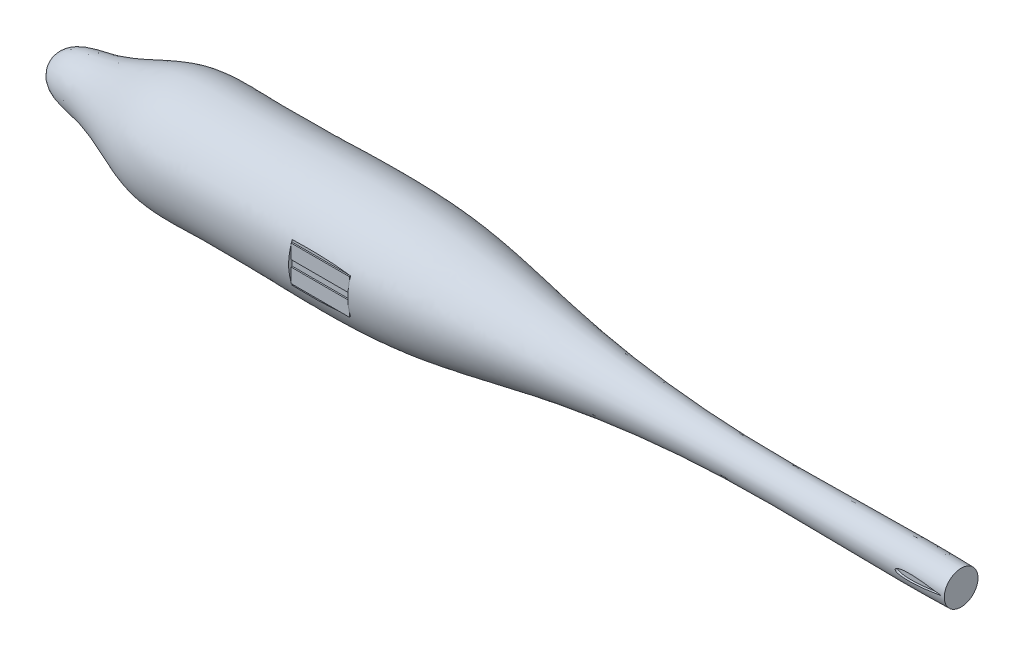
SolidWorks part; units mm, degrees
material "EPP"
ref_plane "Front Plane" through (0, 0, 0) normal (0, 0, 1) x (1, 0, 0)
ref_plane "Top Plane" through (0, 0, 0) normal (0, 1, 0) x (1, 0, 0)
ref_plane "Right Plane" through (0, 0, 0) normal (1, 0, 0) x (0, 0, -1)
sketch "Sketch1" plane through (0, 0, 0) normal (0, 0, 1) x (1, 0, 0)
  line L1 (1400, 97.6339) -> (0, 97.6339) construction
  line L3 (0, 0) -> (1400, 0) construction
  line L6 (1400, 0) -> (1400, 25.997)
  line L7 (0, 0) -> (12.8869, 0)
  line L8 (1388.532, 14.96) -> (1387.1201, 0)
  line L9 (1387.1201, 0) -> (1400, 0)
  spline S0 degree 3 poles (0, 0) (6.0079, 35.1205) (87.5704, 35.98) (174.2855, 89.8849) (355.2298, 80.4635) (551.199, 98.1903) (802.5668, 43.0656) (1072.4121, 17.7479) (1281.1497, 28.8593) (1400, 25.997) knots 0 0 0 0 0.060909 0.147322 0.213189 0.431417 0.561861 0.75012 1 1 1 1
  spline S1 degree 3 poles (12.8869, 0) (12.2702, 24.1237) (42.0071, 17.5904) (77.1548, 41.2159) (129.1678, 36.1628) (178.7554, 69.0831) (233.9908, 66.7109) (368.4506, 69.0999) (548.637, 76.3709) (801.0206, 37.1712) (1065.8549, -5.42) (1273.601, 25.8064) (1388.532, 14.96) knots 0 0 0 0 0.033016 0.050942 0.089125 0.13776 0.171792 0.205001 0.427814 0.55541 0.752934 1 1 1 1
  dimension "D1" = 8
  dimension "D2" = 17.7948
revolve "Revolve2" add sketch "Sketch1" angle 360 about L3
ref_plane "Plane1" through (0, 0, 88) normal (0, 0, 1) x (1, 0, 0)
sketch "Sketch5" plane through (0, 0, 88) normal (0, 0, 1) x (1, 0, 0)
  line L0 (0, 0) -> (1400, 0) construction
  line L1 (450, 100) -> (540, 100)
  line L2 (450, 100) -> (450, -100)
  line L3 (450, -100) -> (540, -100)
  line L4 (540, 100) -> (540, -100)
  line L5 (450, 100) -> (540, -100) construction
  line L6 (450, -100) -> (540, 100) construction
  line L7 (1400, -25.997) -> (1400, 25.997) construction
  point P0 (495, 0)
  dimension "D1" = 450
  dimension "D2" = 90
  dimension "D3" = 200
sketch "Sketch7" plane through (0, 0, 88) normal (0, 0, 1) x (1, 0, 0)
  line L1 (1330.1015, 25) -> (1400.1015, 25)
  line L2 (1330.1015, 25) -> (1330.1015, -25)
  line L3 (1330.1015, -25) -> (1400.1015, -25)
  line L4 (1400.1015, 25) -> (1400.1015, -25)
  line L5 (1330.1015, 25) -> (1400.1015, -25) construction
  line L6 (1330.1015, -25) -> (1400.1015, 25) construction
  point P0 (1365.1015, 0)
extrude "Cut-Extrude4" cut sketch "Sketch5" against normal blind 6.5
sketch "Sketch8" plane through (0, 0, 81.5) normal (0, 0, 1) x (1, 0, 0)
  line L0 (450, 0) -> (540, 0) construction
  line L1 (450, 30.5883) -> (450, -30.5883) construction
  line L2 (540, 27.0452) -> (540, -27.0452) construction
  line L3 (540, -27.0452) -> (540, 27.0452) construction
  line L4 (450, 5) -> (540, 5)
  line L5 (450, 5) -> (450, -5)
  line L6 (450, -5) -> (540, -5)
  line L7 (540, 5) -> (540, -5)
  line L8 (450, 5) -> (540, -5) construction
  line L9 (450, -5) -> (540, 5) construction
  line L11 (540, -27.0452) -> (450, -27.0452)
  line L12 (540, -27.0452) -> (540, -5)
  line L13 (540, -5) -> (450, -5)
  line L14 (450, -27.0452) -> (450, -5)
  line L15 (540, 27.0452) -> (450, 27.0452)
  line L16 (540, 27.0452) -> (540, 5)
  line L17 (540, 5) -> (450, 5)
  line L18 (450, 27.0452) -> (450, 5)
  point P6 (495, 0)
  line M2 (450, 30.5883) -> (450, -30.5883)
  line M4 (540, -27.0452) -> (540, 27.0452)
  dimension "D1" = 10
  dimension "D2" = 22.0452
extrude "Boss-Extrude1" add sketch "Sketch8" along normal blind 2 contours L15 L4 M4 M2 | L11 L6 M4 M2 region at (495, 16.0226, 81.5) region at (495, -16.0226, 81.5)
curve "Curve4"
  spline degree 3 poles (1395, 0.1106, 88) (1393.8337, 0.3112, 88) (1391.503, 0.7122, 88) (1386.8387, 1.4577, 88) (1381.0079, 2.3135, 88) (1374.0074, 3.2252, 88) (1367.0075, 4.0161, 88) (1360.0075, 4.6625, 88) (1353.0064, 5.1217, 88) (1347.1673, 5.2834, 88) (1342.498, 5.2197, 88) (1338.9941, 5.0466, 88) (1335.4854, 4.7134, 88) (1332.5643, 4.2469, 88) (1330.2314, 3.6922, 88) (1328.4601, 3.1359, 88) (1326.971, 2.4608, 88) (1325.6343, 1.5675, 88) (1324.5974, 0, 88) (1325.6343, -1.5675, 88) (1326.971, -2.4608, 88) (1328.4601, -3.1359, 88) (1330.2314, -3.6922, 88) (1332.5643, -4.2469, 88) (1335.4854, -4.7134, 88) (1338.9941, -5.0466, 88) (1342.498, -5.2197, 88) (1347.1673, -5.2834, 88) (1353.0064, -5.1217, 88) (1360.0075, -4.6625, 88) (1367.0075, -4.0161, 88) (1374.0074, -3.2252, 88) (1381.0079, -2.3135, 88) (1386.8387, -1.4577, 88) (1391.503, -0.7122, 88) (1393.8337, -0.3112, 88) (1395, -0.1106, 88) knots 0 0 0 0 0.024684 0.04933 0.098522 0.147602 0.196578 0.24545 0.294219 0.342904 0.367241 0.391608 0.416059 0.440726 0.453243 0.466028 0.479473 0.486972 0.5 0.513028 0.520527 0.533972 0.546757 0.559274 0.583941 0.608392 0.632759 0.657096 0.705781 0.75455 0.803422 0.852398 0.901478 0.95067 0.975316 1 1 1 1
sketch "Sketch14" plane through (0, 0, 88) normal (0, 0, 1) x (1, 0, 0)
  line L0 (1395, 0.1106) -> (1395, -0.1106)
  spline S0 degree 3 poles (1950.8551, 1916.4205) (1541.7499, -55.83) (1468.1035, -11.5304) (1386.8387, 1.4577) (1381.0079, 2.3135) (1374.0074, 3.2252) (1367.0075, 4.0161) (1360.0075, 4.6625) (1353.0064, 5.1217) (1347.1673, 5.2834) (1342.498, 5.2197) (1338.9941, 5.0466) (1335.4854, 4.7134) (1332.5643, 4.2469) (1330.2314, 3.6922) (1328.4601, 3.1359) (1326.971, 2.4608) (1325.6343, 1.5675) (1324.5974, 0) (1325.6343, -1.5675) (1326.971, -2.4608) (1328.4601, -3.1359) (1330.2314, -3.6922) (1332.5643, -4.2469) (1335.4854, -4.7134) (1338.9941, -5.0466) (1342.498, -5.2197) (1347.1673, -5.2834) (1353.0064, -5.1217) (1360.0075, -4.6625) (1367.0075, -4.0161) (1374.0074, -3.2252) (1381.0079, -2.3135) (1386.8387, -1.4577) (1468.103, 11.5303) (1541.749, 55.8295) (1950.8476, -1916.3842) knots -1.618016 -1.618016 -1.618016 -1.618016 0.024684 0.04933 0.098522 0.147602 0.196578 0.24545 0.294219 0.342904 0.367241 0.391608 0.416059 0.440726 0.453243 0.466028 0.479473 0.486972 0.5 0.513028 0.520527 0.533972 0.546757 0.559274 0.583941 0.608392 0.632759 0.657096 0.705781 0.75455 0.803422 0.852398 0.901478 0.95067 0.975316 2.618006 2.618006 2.618006 2.618006 only from (1395, 0.1106) to (1395, -0.1106) construction
  spline S1 degree 3 poles (1395, 0.1106) (1393.8337, 0.3112) (1391.503, 0.7122) (1386.8387, 1.4577) (1381.0079, 2.3135) (1374.0074, 3.2252) (1367.0075, 4.0161) (1360.0075, 4.6625) (1353.0064, 5.1217) (1347.1673, 5.2834) (1342.498, 5.2197) (1338.9941, 5.0466) (1335.4854, 4.7134) (1332.5643, 4.2469) (1330.2314, 3.6922) (1328.4601, 3.1359) (1326.971, 2.4608) (1325.6343, 1.5675) (1324.5974, 0) (1325.6343, -1.5675) (1326.971, -2.4608) (1328.4601, -3.1359) (1330.2314, -3.6922) (1332.5643, -4.2469) (1335.4854, -4.7134) (1338.9941, -5.0466) (1342.498, -5.2197) (1347.1673, -5.2834) (1353.0064, -5.1217) (1360.0075, -4.6625) (1367.0075, -4.0161) (1374.0074, -3.2252) (1381.0079, -2.3135) (1386.8387, -1.4577) (1391.503, -0.7122) (1393.8337, -0.3112) (1395, -0.1106) knots 0 0 0 0 0.024684 0.04933 0.098522 0.147602 0.196578 0.24545 0.294219 0.342904 0.367241 0.391608 0.416059 0.440726 0.453243 0.466028 0.479473 0.486972 0.5 0.513028 0.520527 0.533972 0.546757 0.559274 0.583941 0.608392 0.632759 0.657096 0.705781 0.75455 0.803422 0.852398 0.901478 0.95067 0.975316 1 1 1 1
extrude "Cut-Extrude7" cut sketch "Sketch14" against normal blind 65
